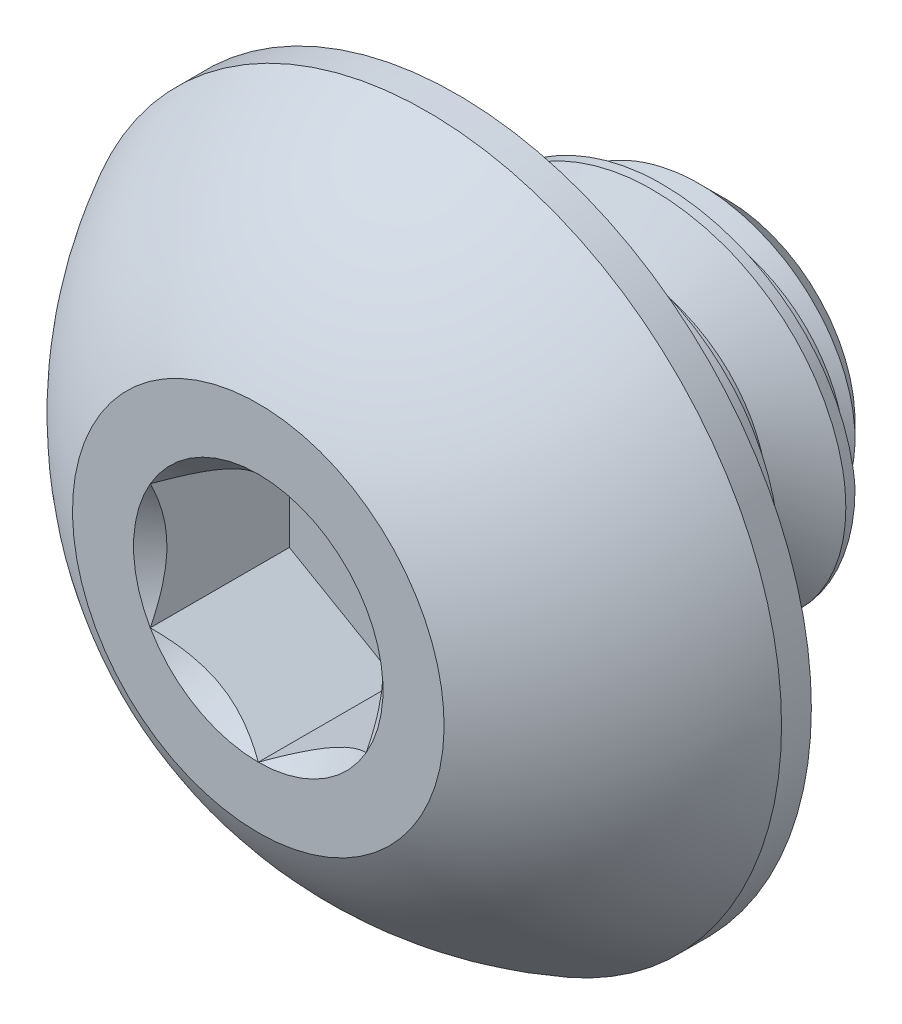
SolidWorks part; units mm, degrees
ref_plane "Front" through (0, 0, 0) normal (0, 0, 1) x (1, 0, 0)
ref_plane "Top" through (0, 0, 0) normal (0, 1, 0) x (1, 0, 0)
ref_plane "Right" through (0, 0, 0) normal (1, 0, 0) x (0, 0, -1)
sketch "Sketch1" plane through (0, 0, 0) normal (1, 0, 0) x (0, 0, -1)
  line L2 (1.1684, 1.0922) -> (2.7559, 1.0922)
  line L3 (2.7559, 1.0922) -> (2.7559, 0)
  line L4 (2.7559, 0) -> (1.1684, 0)
  line L6 (0.9931, 2.0828) -> (1.1684, 2.0828) construction
  line L7 (2.7559, 1.0922) -> (2.7559, -1.0922) construction
  line L8 (0, 0) -> (1.1684, 0) construction
  line L9 (1.1684, 2.0828) -> (1.1684, -2.0828) construction
  line L11 (1.1684, 1.0922) -> (1.1684, 0)
  line L13 (0, 0.635) -> (0, -0.635) construction
  line L14 (0, 0.635) -> (0, 1.0922) construction
  arc A3 (0, 1.0922) -> (0.9931, 2.0828) centre (2.08, 0) cw construction
  dimension "D1" = 0.1753
  dimension "Head Ht" = 1.1684
  dimension "Head Dia" = 4.1656
  dimension "Dia" = 2.1844
  dimension "Lg" = 1.5875
  dimension "Hex" = 1.27
revolve "Revolve1" add sketch "Sketch1" angle 360 mid plane about L4
sketch "Sketch3" plane through (0, 0, -2.7559) normal (0, 0, -1) x (-1, 0, 0)
  circle A0 centre (0, 0) radius 1.0922
curve "Helix/Spiral1" pitch 0.4536 height 2.0411 radius 1.0922 centre (0, 0, -2.7559) axis (0, 0, 1) start towards (0, 1, 0)
sketch "Sketch2" plane through (0, 0, 0) normal (1, 0, 0) x (0, 0, -1)
  line L0 (2.7559, 1.0922) -> (3.1528, 1.0922)
  line L1 (3.1528, 1.0922) -> (2.9827, 0.7976)
  line L2 (2.9827, 0.7976) -> (2.926, 0.7976)
  line L3 (2.926, 0.7976) -> (2.7559, 1.0922)
  line L4 (2.8409, 0.9449) -> (3.0677, 0.9449) construction
  dimension "D1" = 60
  dimension "D2" = 0.0567
  dimension "D3" = 0.2268
chamfer "Chamfer1" distance 0.3402 angle 45 1 edges at (0, 1.0922, -2.7559)
sweep "Cut-Sweep1" cut profiles "Sketch2" path "Helix/Spiral1"
sketch "Sketch7" plane through (0, 0, 0) normal (1, 0, 0) x (0, 0, -1)
  line L6 (0.9931, 2.0828) -> (1.1684, 2.0828) construction
  line L8 (0, 0) -> (1.1684, 0) construction
  line L11 (1.1684, 2.0828) -> (1.1684, -2.0828) construction
  line L12 (0.9931, 2.0828) -> (1.1684, 2.0828)
  line L13 (0, 0) -> (1.1684, 0)
  line L14 (0, 0.635) -> (0, -0.635) construction
  line L15 (1.1684, 2.0828) -> (1.1684, 0)
  line L16 (0, 1.0922) -> (0, 0)
  arc A2 (0.9931, 2.0828) -> (0, 1.0922) centre (2.08, 0) ccw construction
  arc A3 (0.9931, 2.0828) -> (0, 1.0922) centre (2.08, 0) ccw
revolve "Revolve2" add sketch "Sketch7" angle 360 mid plane about L13
sketch "Sketch5" plane through (0, 0, 0) normal (0, 0, 1) x (1, 0, 0)
  line L1 (0.635, -0.3666) -> (0.635, 0.3666)
  line L2 (0.635, 0.3666) -> (0, 0.7332)
  line L3 (0, 0.7332) -> (-0.635, 0.3666)
  line L4 (-0.635, 0.3666) -> (-0.635, -0.3666)
  line L5 (-0.635, -0.3666) -> (0, -0.7332)
  line L6 (0, -0.7332) -> (0.635, -0.3666)
  circle A0 centre (0, 0) radius 0.635 construction
extrude "Cut-Extrude2" cut sketch "Sketch5" against normal blind 0.8179
sketch "Sketch6" plane through (0, 0, 0) normal (0, 0, 1) x (1, 0, 0)
  circle A0 centre (0, 0) radius 0.7332
extrude "Cut-Extrude3" cut sketch "Sketch6" against normal blind 0.8179 draft 45
sketch "Sketch9" [suppressed] plane through (0, 0, -4.2164) normal (0, 0, 1) x (1, 0, 0)
  circle A2 centre (0, 0) radius 3.9687
extrude "Boss-Extrude2" [suppressed] add sketch "Sketch9" against normal offset from surface (9.525 mm away) 28.575 up to face at (0, 0.752, -2.7559)
sketch "Sketch10" plane through (0, 0, 0) normal (1, 0, 0) x (0, 0, -1)
  line L0 (2.7559, 1.0922) -> (2.7559, -1.0922) construction
  point P0 (2.0755, -1.0922)
  dimension "D1" = 0.6804
equation "\"D3@Helix/Spiral1\" = \"Lg@Sketch1\" + \"D4@Helix/Spiral1\""
equation "\"D2@Sketch2\" = \"D4@Helix/Spiral1\" * .125"
equation "\"D3@Sketch2\" = \"D4@Helix/Spiral1\" * .5"
equation "\"D1@Chamfer1\" = \"D4@Helix/Spiral1\" * .75"
equation "\"D1@Cut-Extrude2\" = \"Head Ht@Sketch1\" * .7"
equation "\"D1@Sketch1\" = \"Head Ht@Sketch1\" * .15"
equation "\"D1@Sketch10\" = \"D4@Helix/Spiral1\" * 1.5"
equation "\"D1@Cut-Extrude3\" = \"D1@Cut-Extrude2\""
